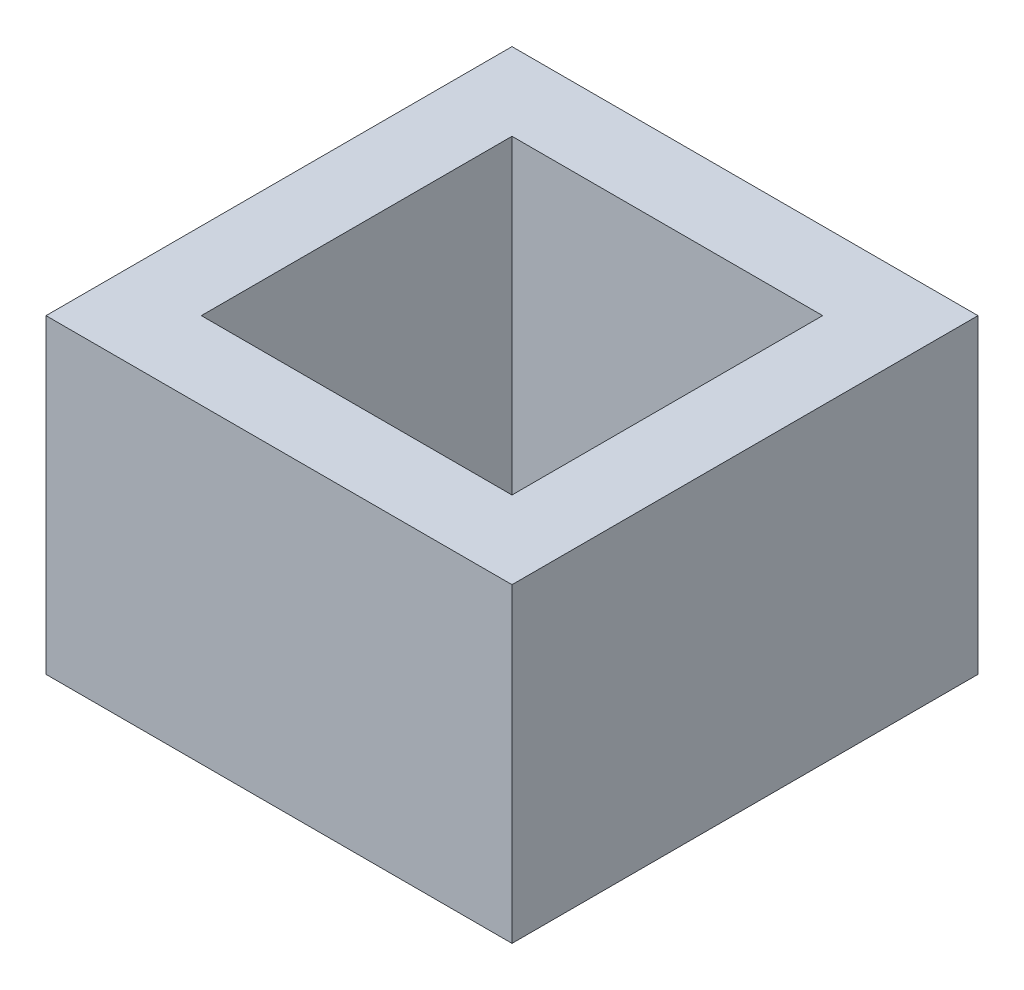
SolidWorks part; units mm, degrees
ref_plane "Front Plane" through (0, 0, 0) normal (0, 0, 1) x (1, 0, 0)
ref_plane "Top Plane" through (0, 0, 0) normal (0, 1, 0) x (1, 0, 0)
ref_plane "Right Plane" through (0, 0, 0) normal (1, 0, 0) x (0, 0, -1)
sketch "Sketch1" plane through (0, 0, 0) normal (0, 1, 0) x (1, 0, 0)
  line L0 (-15, -15) -> (-15, 15)
  line L1 (10, -10) -> (-10, -10)
  line L2 (10, -10) -> (10, 10)
  line L3 (10, 10) -> (-10, 10)
  line L4 (-10, -10) -> (-10, 10)
  line L5 (10, -10) -> (-10, 10) construction
  line L6 (10, 10) -> (-10, -10) construction
  line L7 (15, 15) -> (-15, 15)
  line L8 (15, -15) -> (15, 15)
  line L9 (15, -15) -> (-15, -15)
  point P0 (0, 0)
  dimension "D1" = 20
  dimension "D2" = 20
  dimension "D3" = 5
extrude "Boss-Extrude1" add sketch "Sketch1" along normal blind 20
